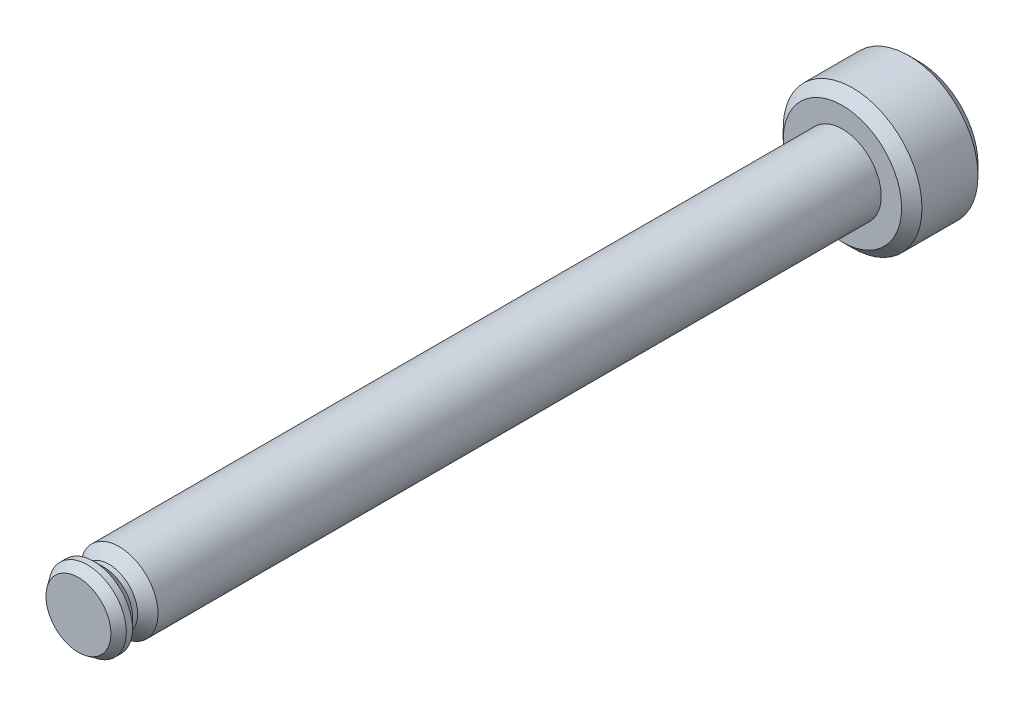
SolidWorks part; units mm, degrees
ref_plane "Front" through (0, 0, 0) normal (0, 0, 1) x (1, 0, 0)
ref_plane "Top" through (0, 0, 0) normal (0, 1, 0) x (1, 0, 0)
ref_plane "Right" through (0, 0, 0) normal (1, 0, 0) x (0, 0, -1)
sketch "Sketch2" plane through (0, 0, 0) normal (0, 0, 1) x (1, 0, 0)
  circle A0 centre (0, 0) radius 1.525
  dimension "D1" = 3.05
extrude "Shaft" add sketch "Sketch2" along normal blind 30
sketch "Sketch5" plane through (0, 0, 0) normal (0, 0, 1) x (1, 0, 0)
  circle A0 centre (0, 0) radius 2.725
  dimension "D1" = 5.45
extrude "Head" add sketch "Sketch5" against normal blind 3
sketch "Sketch4" plane through (0, 0, 0) normal (1, 0, 0) x (0, 0, -1)
  line L0 (0, 0) -> (-18.85, 0) construction
  line L1 (-18.85, 0) -> (-18.85, 4.3666) construction
  line L2 (-19.35, 1.525) -> (-18.35, 1.525)
  line L3 (0, 1.525) -> (-30, 1.525) construction
  line L6 (-18.35, 1.525) -> (-18.75, 1.125)
  line L7 (-18.75, 1.125) -> (-18.95, 1.125)
  line L8 (-18.95, 1.125) -> (-19.35, 1.525)
  line L10 (-18.85, 50) -> (-18.85, -50) construction
  dimension "D2" = 1
  dimension "D3" = 45
  dimension "D4" = 0.4
revolve "e-Clip Notch Short" [suppressed] cut sketch "Sketch4" angle 360 about L0
chamfer "Chamfer1" distance 0.25 angle 55 1 edges at (1.525, 0, 30) first distance on face at (1.525, 0, 30)
chamfer "Deburs" distance 0.4 angle 45 2 edges at (2.725, 0, 0) (2.725, 0, -3)
sketch "Sketch6" plane through (0, 0, 0) normal (1, 0, 0) x (0, 0, -1)
  line L0 (0, 0) -> (-28.9, 0) construction
  line L1 (-28.9, 0) -> (-28.9, 1.125) construction
  line L2 (0, 1.525) -> (-29.643, 1.525) construction
  line L3 (-29.4, 1.525) -> (-28.4, 1.525)
  line L4 (-28.4, 1.525) -> (-28.8, 1.125)
  line L5 (-28.8, 1.125) -> (-29, 1.125)
  line L6 (-29, 1.125) -> (-29.4, 1.525)
  line L7 (-28.9, 1.125) -> (-28.9, 1.525) construction
  line L8 (-19.35, 1.525) -> (-18.35, 1.525) construction
  line L9 (-18.95, 1.125) -> (-19.35, 1.525) construction
  line L10 (-28.9, 50) -> (-28.9, -50) construction
revolve "e-Clip Notch Long" cut sketch "Sketch6" angle 360 about L0
equation "\"D1@Sketch2\"=\"Plastic Hardware OD@Box Assy.Assembly\""
equation "\"D1@Sketch5\"=\"Hardware Head Countersink Diameter@Box Assy.Assembly\"-.3mm"
equation "\"D1@Head\"=\"Countersink Depth@Box Assy.Assembly\""
